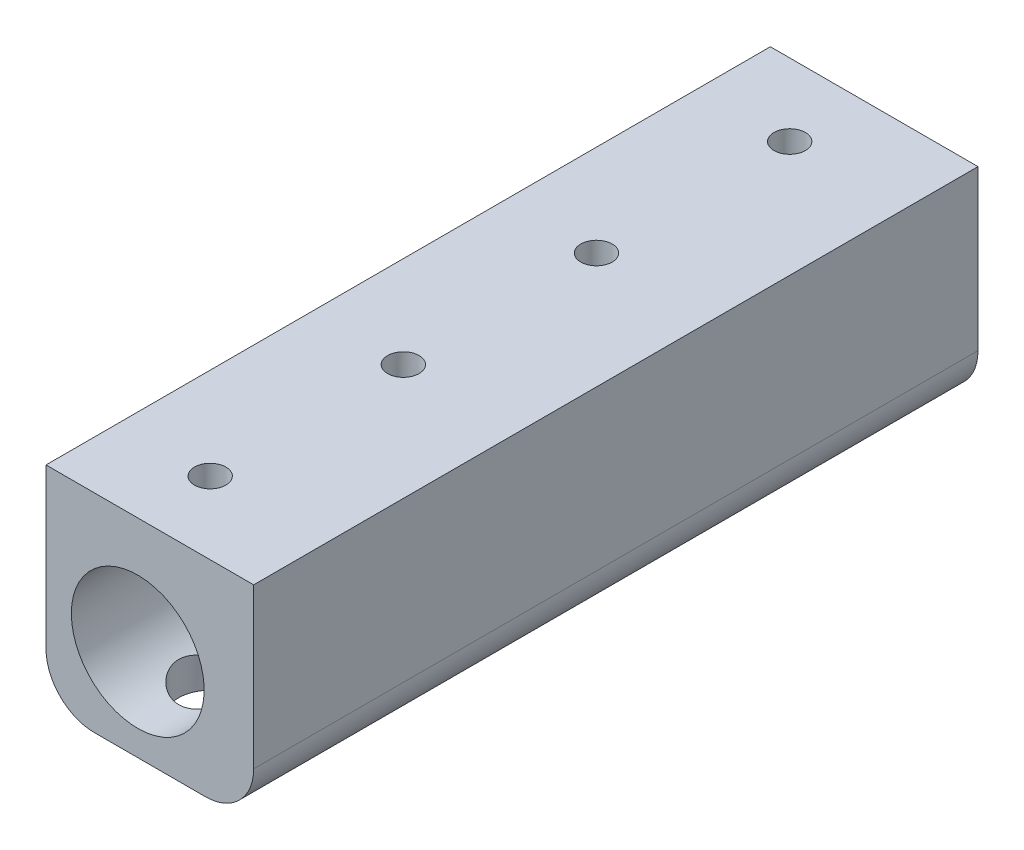
SolidWorks part; units mm, degrees
ref_plane "Front Plane" through (0, 0, 0) normal (0, 0, 1) x (1, 0, 0)
ref_plane "Top Plane" through (0, 0, 0) normal (0, 1, 0) x (1, 0, 0)
ref_plane "Right Plane" through (0, 0, 0) normal (1, 0, 0) x (0, 0, -1)
sketch "Sketch1" plane through (0, 0, 0) normal (0, 0, 1) x (1, 0, 0)
  line L1 (-19, -24) -> (19, -24)
  line L2 (-19, -24) -> (-19, 24)
  line L3 (-19, 24) -> (19, 24)
  line L4 (19, -24) -> (19, 24)
  line L5 (-19, -24) -> (19, 24) construction
  line L6 (-19, 24) -> (19, -24) construction
  line L7 (19, -24) -> (24, -24)
  line L8 (19, -24) -> (19, 35.2)
  line L9 (19, 35.2) -> (24, 35.2)
  line L10 (24, -24) -> (24, 35.2)
  line L11 (19, 35.2) -> (-19, 35.2)
  line L12 (19, 35.2) -> (19, 25.2)
  line L13 (19, 25.2) -> (-19, 25.2)
  line L14 (-19, 35.2) -> (-19, 25.2)
  circle A0 centre (0, 0) radius 13.75
  dimension "D1" = 27.5
  dimension "D2" = 1.2
  dimension "D3" = 48
  dimension "D4" = 38
  dimension "D5" = 5
  dimension "D6" = 10
extrude "Boss-Extrude1" add sketch "Sketch1" along normal blind 230 contours L1 L4 L3 L2 A0 | L11 L14 L13 L8 | L7 L10 L9 L8 L4
sketch "Sketch3" plane through (0, 35.2, 0) normal (0, 1, 0) x (1, 0, 0)
  line L0 (0, 0) -> (0, -230) construction
  line L1 (-19, -230) -> (24, -230) construction
  circle A0 centre (0, -15) radius 6
  circle A1 centre (0, -55) radius 6
  circle A2 centre (0, -95) radius 6
  circle A3 centre (0, -135) radius 6
  circle A4 centre (0, -175) radius 6
  circle A5 centre (0, -215) radius 6
  dimension "D1" = 12
  dimension "D2" = 15
  dimension "D4" = 15
  dimension "D3" = 6
extrude "Cut-Extrude1" cut sketch "Sketch3" against normal blind 0.5
sketch "Sketch4" plane through (0, 35.2, 0) normal (0, 1, 0) x (1, 0, 0)
  line L0 (0, 0) -> (0, -230) construction
  line L1 (-19, -230) -> (24, -230) construction
  circle A0 centre (0, -15) radius 3.25
  circle A1 centre (0, -55) radius 3.25
  circle A2 centre (0, -95) radius 3.25
  circle A3 centre (0, -135) radius 3.25
  circle A4 centre (0, -175) radius 3.25
  circle A5 centre (0, -215) radius 3.25
  dimension "D1" = 6.5
  dimension "D2" = 6
extrude "Cut-Extrude2" cut sketch "Sketch4" against normal through all
sketch "Sketch5" plane through (0, -24, 0) normal (0, -1, 0) x (1, 0, 0)
  line L0 (0, 230) -> (0, 0) construction
  line L1 (-19, 230) -> (24, 230) construction
  circle A0 centre (0, 215) radius 6.5
  circle A1 centre (0, 175) radius 6.5
  circle A2 centre (0, 135) radius 6.5
  circle A3 centre (0, 95) radius 6.5
  circle A4 centre (0, 55) radius 6.5
  circle A5 centre (0, 15) radius 6.5
  dimension "D1" = 13
  dimension "D2" = 6
extrude "Cut-Extrude3" cut sketch "Sketch5" against normal up to next
sketch "Sketch7" plane through (0, 24, 0) normal (0, 1, 0) x (1, 0, 0)
  line L0 (0, 0) -> (0, -230) construction
  line L1 (0, -8.5337) -> (-5.6, -11.7668)
  line L2 (-5.6, -11.7668) -> (-5.6, -18.2332)
  line L3 (-5.6, -18.2332) -> (0, -21.4663)
  line L4 (0, -21.4663) -> (5.6, -18.2332)
  line L5 (5.6, -18.2332) -> (5.6, -11.7668)
  line L6 (5.6, -11.7668) -> (0, -8.5337)
  line L7 (-19, -230) -> (24, -230) construction
  line L8 (0, -48.5337) -> (-5.6, -51.7668)
  line L9 (-5.6, -51.7668) -> (-5.6, -58.2332)
  line L10 (-5.6, -58.2332) -> (0, -61.4663)
  line L11 (0, -61.4663) -> (5.6, -58.2332)
  line L12 (5.6, -58.2332) -> (5.6, -51.7668)
  line L13 (5.6, -51.7668) -> (0, -48.5337)
  line L14 (0, -88.5337) -> (-5.6, -91.7668)
  line L15 (-5.6, -91.7668) -> (-5.6, -98.2332)
  line L16 (-5.6, -98.2332) -> (0, -101.4663)
  line L17 (0, -101.4663) -> (5.6, -98.2332)
  line L18 (5.6, -98.2332) -> (5.6, -91.7668)
  line L19 (5.6, -91.7668) -> (0, -88.5337)
  line L20 (0, -128.5337) -> (-5.6, -131.7668)
  line L21 (-5.6, -131.7668) -> (-5.6, -138.2332)
  line L22 (-5.6, -138.2332) -> (0, -141.4663)
  line L23 (0, -141.4663) -> (5.6, -138.2332)
  line L24 (5.6, -138.2332) -> (5.6, -131.7668)
  line L25 (5.6, -131.7668) -> (0, -128.5337)
  line L26 (0, -168.5337) -> (-5.6, -171.7668)
  line L27 (-5.6, -171.7668) -> (-5.6, -178.2332)
  line L28 (-5.6, -178.2332) -> (0, -181.4663)
  line L29 (0, -181.4663) -> (5.6, -178.2332)
  line L30 (5.6, -178.2332) -> (5.6, -171.7668)
  line L31 (5.6, -171.7668) -> (0, -168.5337)
  line L32 (0, -208.5337) -> (-5.6, -211.7668)
  line L33 (-5.6, -211.7668) -> (-5.6, -218.2332)
  line L34 (-5.6, -218.2332) -> (0, -221.4663)
  line L35 (0, -221.4663) -> (5.6, -218.2332)
  line L36 (5.6, -218.2332) -> (5.6, -211.7668)
  line L37 (5.6, -211.7668) -> (0, -208.5337)
  circle A0 centre (0, -15) radius 5.6 construction
  dimension "D1" = 11.2
  dimension "D2" = 6
extrude "Cut-Extrude4" cut sketch "Sketch7" against normal up to next from offset 5 offset against normal yes
chamfer "Chamfer1" distance 5 angle 45 6 edges at (0, 34.7, 218.25) (0, 34.7, 178.25) (0, 34.7, 138.25) (0, 34.7, 98.25) (0, 34.7, 58.25) (0, 34.7, 18.25)
sketch "Sketch8" plane through (19, 0, 0) normal (-1, 0, 0) x (0, 0, 1)
  line L1 (0, 25.2) -> (230, 25.2)
  line L2 (0, 25.2) -> (0, 24)
  line L3 (0, 24) -> (230, 24)
  line L4 (230, 25.2) -> (230, 24)
extrude "Cut-Extrude6" cut sketch "Sketch8" against normal blind 10
sketch "Sketch9" plane through (0, 24, 0) normal (0, 1, 0) x (1, 0, 0)
  line L0 (24, 0) -> (24, -230) construction
  line L1 (-19, -230) -> (24, -230)
  line L2 (-19, -230) -> (-19, -150)
  line L3 (-19, -150) -> (24, -150)
  line L4 (24, -230) -> (24, -150)
  dimension "D1" = 80
extrude "Cut-Extrude7" cut sketch "Sketch9" against normal through all
sketch "Sketch10" plane through (0, 0, 0) normal (0, 0, -1) x (-1, 0, 0)
  line L0 (19, -24) -> (19, 24) construction
  line L1 (-24, -24) -> (19, -24)
  line L2 (-24, -24) -> (-24, -19)
  line L3 (-24, -19) -> (19, -19)
  line L4 (19, -24) -> (19, -19)
  dimension "D1" = 5
extrude "Cut-Extrude8" cut sketch "Sketch10" against normal through all
fillet "Fillet1" radius 10 2 edges at (-19, -19, 75) (24, -19, 75)
